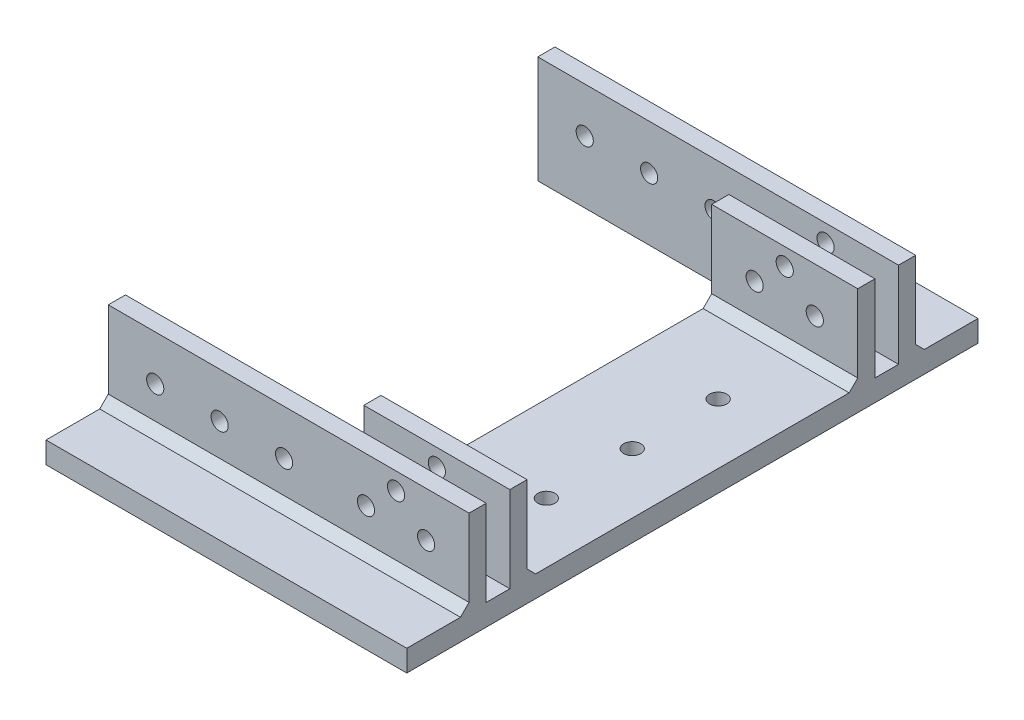
SolidWorks part; units mm, degrees
ref_plane "Front Plane" through (0, 0, 0) normal (0, 0, 1) x (1, 0, 0)
ref_plane "Top Plane" through (0, 0, 0) normal (0, 1, 0) x (1, 0, 0)
ref_plane "Right Plane" through (0, 0, 0) normal (1, 0, 0) x (0, 0, -1)
sketch "Sketch1" plane through (0, 0, 0) normal (0, 1, 0) x (1, 0, 0)
  line L1 (-84.6509, 30.6509) -> (-50.6509, 30.6509)
  line L2 (-84.6509, 30.6509) -> (-84.6509, -102.3491)
  line L3 (-84.6509, -102.3491) -> (-50.6509, -102.3491)
  line L4 (-50.6509, 30.6509) -> (-50.6509, -102.3491)
  dimension "D1" = 34
  dimension "D2" = 133
extrude "Boss-Extrude1" add sketch "Sketch1" along normal blind 5
sketch "Sketch2" plane through (0, 5, 0) normal (0, 1, 0) x (1, 0, 0)
  line L0 (-50.6509, -102.3491) -> (-50.6509, 30.6509) construction
  line L6 (-84.6509, 30.6509) -> (-84.6509, -102.3491) construction
  line L7 (-84.6509, -35.8491) -> (-50.6509, -35.8491) construction
  line L8 (-84.6509, 12.1509) -> (-50.6509, 12.1509)
  line L15 (-84.6509, 12.1509) -> (-84.6509, 16.1509)
  line L16 (-84.6509, 16.1509) -> (-50.6509, 16.1509)
  line L17 (-50.6509, 12.1509) -> (-50.6509, 16.1509)
  line L18 (-84.6509, 2.6509) -> (-50.6509, 2.6509)
  line L19 (-84.6509, 2.6509) -> (-84.6509, 6.6509)
  line L20 (-84.6509, 6.6509) -> (-50.6509, 6.6509)
  line L21 (-50.6509, 2.6509) -> (-50.6509, 6.6509)
  line L22 (-50.6509, -74.3491) -> (-50.6509, -78.3491)
  line L23 (-84.6509, -78.3491) -> (-50.6509, -78.3491)
  line L24 (-84.6509, -74.3491) -> (-84.6509, -78.3491)
  line L25 (-84.6509, -74.3491) -> (-50.6509, -74.3491)
  line L26 (-50.6509, -83.8491) -> (-50.6509, -87.8491)
  line L27 (-84.6509, -87.8491) -> (-50.6509, -87.8491)
  line L28 (-84.6509, -83.8491) -> (-84.6509, -87.8491)
  line L29 (-50.6509, -83.8491) -> (-84.6509, -83.8491)
  line L30 (-67.6509, 30.6509) -> (-67.6509, -102.3491) construction
  line L31 (-50.6509, 30.6509) -> (-84.6509, 30.6509) construction
  line L32 (-84.6509, -102.3491) -> (-50.6509, -102.3491) construction
  dimension "D2" = 4
  dimension "D3" = 42.5
  dimension "D1" = 4
  dimension "D4" = 17
  dimension "D5" = 17
  dimension "D6" = 34
  dimension "D7" = 17
  dimension "D8" = 48
extrude "Boss-Extrude2" add sketch "Sketch2" along normal blind 20
sketch "Sketch3" plane through (0, 5, 0) normal (0, 1, 0) x (1, 0, 0)
  line L0 (-64.6509, 30.6509) -> (-64.6509, -102.3491) construction
  line L1 (-50.6509, 30.6509) -> (-84.6509, 30.6509) construction
  line L2 (-84.6509, -102.3491) -> (-50.6509, -102.3491) construction
  line L3 (-50.6509, -102.3491) -> (-50.6509, -87.8491) construction
  line L4 (-64.6509, -35.8491) -> (13.4519, -35.8491) construction
  circle A0 centre (-64.6509, -35.8491) radius 2
  circle A1 centre (-64.6509, -15.8491) radius 2
  circle A2 centre (-64.6509, -55.8491) radius 2
  dimension "D1" = 4
  dimension "D3" = 4
  dimension "D2" = 14
  dimension "D4" = 20
extrude "Cut-Extrude1" cut sketch "Sketch3" against normal through all both and the other way through all
chamfer "Chamfer1" distance 2 angle 45 4 edges at (-67.6509, 5, 74.3491) (-67.6509, 5, 87.8491) (-67.6509, 5, -16.1509) (-67.6509, 5, -2.6509)
sketch "Sketch6" plane through (0, 0, -16.1509) normal (0, 0, -1) x (-1, 0, 0)
  line L0 (67.6509, 25) -> (67.6509, 8.1) construction
  line L1 (50.6509, 25) -> (84.6509, 25) construction
  circle A0 centre (60.6509, 14.5) radius 2
  circle A1 centre (74.6509, 14.5) radius 2
  circle A2 centre (67.6509, 21) radius 2
  dimension "D1" = 4
  dimension "D2" = 4
  dimension "D3" = 4
extrude "Cut-Extrude2" cut sketch "Sketch6" against normal through all both and the other way through all
sketch "Sketch7" plane through (-84.6509, 0, 0) normal (-1, 0, 0) x (0, 0, 1)
  line L0 (-30.6509, 0) -> (-30.6509, 5)
  line L1 (-30.6509, 5) -> (-18.1509, 5)
  line L2 (-18.1509, 5) -> (-16.1509, 7)
  line L3 (-16.1509, 7) -> (-16.1509, 25)
  line L4 (-16.1509, 25) -> (-12.1509, 25)
  line L5 (-12.1509, 25) -> (-12.1509, 5)
  line L6 (-12.1509, 5) -> (-12.1509, 0)
  line L7 (-30.6509, 0) -> (102.3491, 0) construction
  line L8 (-12.1509, 0) -> (-30.6509, 0)
  line L9 (35.8491, 5) -> (35.8491, -12.0028) construction
  line L10 (-0.6509, 5) -> (72.3491, 5) construction
  line L11 (83.8491, 0) -> (102.3491, 0)
  line L12 (83.8491, 5) -> (83.8491, 0)
  line L13 (83.8491, 25) -> (83.8491, 5)
  line L14 (87.8491, 25) -> (83.8491, 25)
  line L15 (87.8491, 7) -> (87.8491, 25)
  line L16 (89.8491, 5) -> (87.8491, 7)
  line L17 (102.3491, 5) -> (89.8491, 5)
  line L18 (102.3491, 0) -> (102.3491, 5)
extrude "Boss-Extrude3" add sketch "Sketch7" along normal blind 50 from surface starting at face at (-84.6509, 11.5833, 35.8491)
sketch "Sketch8" plane through (0, 0, -16.1509) normal (0, 0, -1) x (-1, 0, 0)
  line L0 (60.6509, 14.5) -> (134.6509, 14.5) construction
  line L1 (134.6509, 25) -> (134.6509, 7) construction
  circle A0 centre (123.7195, 14.5) radius 2
  circle A1 centre (108.7195, 14.5) radius 2
  circle A2 centre (93.7195, 14.5) radius 2
  dimension "D1" = 4
  dimension "D2" = 3
extrude "Cut-Extrude3" cut sketch "Sketch8" against normal through all both and the other way through all
